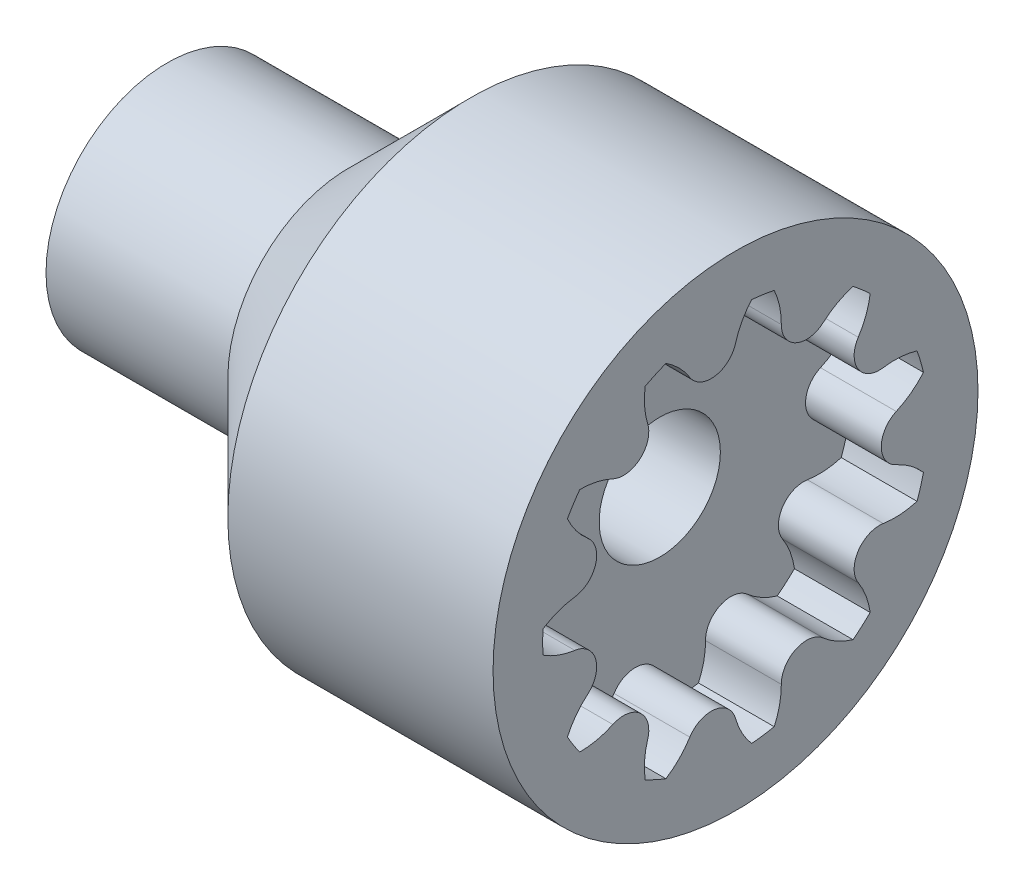
SolidWorks part; units mm, degrees
ref_plane "Front Plane" through (0, 0, 0) normal (1, 0, 0) x (0, 1, 0)
ref_plane "Top Plane" through (0, 0, 0) normal (0, 0, 1) x (0, 1, 0)
ref_plane "Right Plane" through (0, 0, 0) normal (0, 1, 0) x (-1, 0, 0)
sketch "Sketch1" plane through (0, 0, 0) normal (1, 0, 0) x (0, 1, 0)
  arc A0 (-4.4531, -9.7448) -> (-4.4365, -9.5817) centre (-6.1017, -9.4944) ccw
  arc A1 (-1.4481, -10.4592) -> (-1.5223, -10.6054) centre (0, -11.2861) ccw
  arc A2 (1.4481, -10.4592) -> (-1.4481, -10.4592) centre (0, -11.2861) ccw
  arc A3 (1.5223, -10.6054) -> (1.4481, -10.4592) centre (0, -11.2861) ccw
  arc A4 (4.4365, -9.5817) -> (4.4531, -9.7448) centre (6.1017, -9.4944) ccw
  arc A5 (7.0143, -8.0988) -> (6.8728, -8.0159) centre (6.1017, -9.4944) ccw
  arc A6 (10.2794, -3.0209) -> (10.1155, -3.0277) centre (10.2662, -4.6884) ccw
  arc A7 (8.9125, -5.6621) -> (9.0146, -5.7904) centre (10.2662, -4.6884) ccw
  arc A8 (10.5588, 0.0552) -> (10.7141, 0.0025) centre (11.1712, 1.6062) ccw
  arc A9 (10.2808, 3.0161) -> (10.1466, 2.9218) centre (11.1712, 1.6062) ccw
  arc A10 (10.2794, -3.0209) -> (12.4668, -2.5526) centre (10.3203, 2.13) ccw
  arc A11 (10.1155, -3.0277) -> (8.9125, -5.6621) centre (10.2662, -4.6884) ccw
  arc A12 (10.0931, -7.7502) -> (9.0146, -5.7904) centre (5.1486, -9.1944) ccw
  arc A13 (9.1077, -8.8874) -> (10.0931, -7.7502) centre (0, 0) ccw
  arc A14 (7.0143, -8.0988) -> (9.1077, -8.8874) centre (9.8335, -3.7877) ccw
  arc A15 (6.8728, -8.0159) -> (4.4365, -9.5817) centre (6.1017, -9.4944) ccw
  arc A16 (4.3008, -11.9766) -> (4.4531, -9.7448) centre (-0.6396, -10.5183) ccw
  arc A17 (2.857, -12.4005) -> (4.3008, -11.9766) centre (0, 0) ccw
  arc A18 (1.5223, -10.6054) -> (2.857, -12.4005) centre (6.2247, -8.5028) ccw
  arc A19 (-2.857, -12.4005) -> (-1.5223, -10.6054) centre (-6.2247, -8.5028) ccw
  arc A20 (-4.3008, -11.9766) -> (-2.857, -12.4005) centre (0, 0) ccw
  arc A21 (-4.4531, -9.7448) -> (-4.3008, -11.9766) centre (0.6396, -10.5183) ccw
  arc A22 (12.4668, -2.5526) -> (12.6809, -1.0631) centre (0, 0) ccw
  arc A23 (12.6809, -1.0631) -> (10.7141, 0.0025) centre (9.3021, -4.9513) ccw
  arc A24 (10.1466, 2.9218) -> (10.5588, 0.0552) centre (11.1712, 1.6062) ccw
  arc A25 (10.2808, 3.0161) -> (11.8677, 4.5927) centre (7.5304, 7.3714) ccw
  arc A26 (11.8677, 4.5927) -> (11.2426, 5.9615) centre (0, 0) ccw
  arc A27 (-6.8728, -8.0159) -> (-7.0143, -8.0988) centre (-6.1017, -9.4944) ccw
  arc A28 (-9.0146, -5.7904) -> (-8.9125, -5.6621) centre (-10.2662, -4.6884) ccw
  arc A29 (-10.1155, -3.0277) -> (-10.2794, -3.0209) centre (-10.2662, -4.6884) ccw
  arc A30 (-10.7141, 0.0025) -> (-10.5588, 0.0552) centre (-11.1712, 1.6062) ccw
  arc A31 (-10.1466, 2.9218) -> (-10.2808, 3.0161) centre (-11.1712, 1.6062) ccw
  arc A32 (-4.4365, -9.5817) -> (-6.8728, -8.0159) centre (-6.1017, -9.4944) ccw
  arc A33 (-9.1077, -8.8874) -> (-7.0143, -8.0988) centre (-9.8335, -3.7877) ccw
  arc A34 (-10.0931, -7.7502) -> (-9.1077, -8.8874) centre (0, 0) ccw
  arc A35 (-9.0146, -5.7904) -> (-10.0931, -7.7502) centre (-5.1486, -9.1944) ccw
  arc A36 (-8.9125, -5.6621) -> (-10.1155, -3.0277) centre (-10.2662, -4.6884) ccw
  arc A37 (-12.4668, -2.5526) -> (-10.2794, -3.0209) centre (-10.3203, 2.13) ccw
  arc A38 (-12.6809, -1.0631) -> (-12.4668, -2.5526) centre (0, 0) ccw
  arc A39 (-10.7141, 0.0025) -> (-12.6809, -1.0631) centre (-9.3021, -4.9513) ccw
  arc A40 (-10.5588, 0.0552) -> (-10.1466, 2.9218) centre (-11.1712, 1.6062) ccw
  arc A41 (-11.8677, 4.5927) -> (-10.2808, 3.0161) centre (-7.5304, 7.3714) ccw
  arc A42 (-9.0119, 5.7946) -> (-8.8528, 5.7549) centre (-8.5294, 7.3908) ccw
  arc A43 (-6.9562, 7.9437) -> (-7.0182, 8.0955) centre (-8.5294, 7.3908) ccw
  arc A44 (-4.4485, 9.7469) -> (-4.3361, 9.6275) centre (-3.1797, 10.8289) ccw
  arc A45 (-1.5573, 10.4435) -> (-1.5273, 10.6047) centre (-3.1797, 10.8289) ccw
  arc A46 (8.8528, 5.7549) -> (9.0119, 5.7946) centre (8.5294, 7.3908) ccw
  arc A47 (7.0182, 8.0955) -> (6.9562, 7.9437) centre (8.5294, 7.3908) ccw
  arc A48 (11.2426, 5.9615) -> (9.0119, 5.7946) centre (10.5023, 0.8638) ccw
  arc A49 (6.9562, 7.9437) -> (8.8528, 5.7549) centre (8.5294, 7.3908) ccw
  arc A50 (7.0182, 8.0955) -> (7.5008, 10.2798) centre (2.3497, 10.2725) ccw
  arc A51 (7.5008, 10.2798) -> (6.2349, 11.0933) centre (0, 0) ccw
  arc A52 (4.3361, 9.6275) -> (4.4485, 9.7469) centre (3.1797, 10.8289) ccw
  arc A53 (1.5273, 10.6047) -> (1.5573, 10.4435) centre (3.1797, 10.8289) ccw
  arc A54 (6.2349, 11.0933) -> (4.4485, 9.7469) centre (8.3681, 6.4047) ccw
  arc A55 (1.5573, 10.4435) -> (4.3361, 9.6275) centre (3.1797, 10.8289) ccw
  arc A56 (1.5273, 10.6047) -> (0.7524, 12.7031) centre (-3.5771, 9.9121) ccw
  arc A57 (0.7524, 12.7031) -> (0, 12.7254) centre (0, 0) ccw
  arc A58 (0, 12.7254) -> (-0.7524, 12.7031) centre (0, 0) ccw
  arc A59 (-0.7524, 12.7031) -> (-1.5273, 10.6047) centre (3.5771, 9.9121) ccw
  arc A60 (-4.3361, 9.6275) -> (-1.5573, 10.4435) centre (-3.1797, 10.8289) ccw
  arc A61 (-4.4485, 9.7469) -> (-6.2349, 11.0933) centre (-8.3681, 6.4047) ccw
  arc A62 (-6.2349, 11.0933) -> (-7.5008, 10.2798) centre (0, 0) ccw
  arc A63 (-7.5008, 10.2798) -> (-7.0182, 8.0955) centre (-2.3497, 10.2725) ccw
  arc A64 (-8.8528, 5.7549) -> (-6.9562, 7.9437) centre (-8.5294, 7.3908) ccw
  arc A65 (-9.0119, 5.7946) -> (-11.2426, 5.9615) centre (-10.5023, 0.8638) ccw
  arc A66 (-11.2426, 5.9615) -> (-11.8677, 4.5927) centre (0, 0) ccw
  circle A67 centre (0, 0) radius 16
  circle A68 centre (0, 0) radius 4
extrude "Boss-Extrude1" add sketch "Sketch1" against normal blind 12.5 contours A67 | A68
extrude "Boss-Extrude2" add sketch "Sketch1<3>" along normal blind 5 contours A67 | A32 A27 A33 A34 A35 A28 A36 A29 A37 A38 A39 A30 A40 A31 A41 A66 A65 A42 A64 A43 A63 A62 A61 A44 A60 A45 A59 A58 A57 A56 A53 A55 A52 A54 A51 A50 A47 A49 A46 A48 A26 A25 A9 A24 A8 A23 A22 A10 A6 A11 A7 A12 A13 A14 A5 A15 A4 A16 A17 A18 A3 A2 A1 A19 A20 A21 A0
sketch "Sketch1<3>" plane through (0, 0, 0) normal (1, 0, 0) x (0, 1, 0) same geometry as "Sketch1"
sketch "Sketch2" plane through (-12.5, 0, 0) normal (-1, 0, 0) x (0, -1, 0)
  circle A0 centre (0, 0) radius 16
extrude "Boss-Extrude3" add sketch "Sketch2" along normal blind 8 draft 45
sketch "Sketch4" plane through (-20.5, 0, 0) normal (-1, 0, 0) x (0, -1, 0)
  line L1 (-1.19, 5.19) -> (1.19, 5.19)
  line L2 (-1.19, 5.19) -> (-1.19, 2.81)
  line L3 (-1.19, 2.81) -> (1.19, 2.81)
  line L4 (1.19, 5.19) -> (1.19, 2.81)
  line L5 (-1.19, 5.19) -> (1.19, 2.81) construction
  line L6 (-1.19, 2.81) -> (1.19, 5.19) construction
  circle A0 centre (0, 0) radius 4
  circle A1 centre (0, 0) radius 8
  point P3 (0, 4)
  circle M7 centre (0, 0) radius 8
  dimension "D1" = 2.38
  dimension "D2" = 2.38
extrude "Boss-Extrude4" add sketch "Sketch4" along normal blind 12 contours A0 L2 L1 L4 M7 region at (-20.5, 7.7737, 0)
